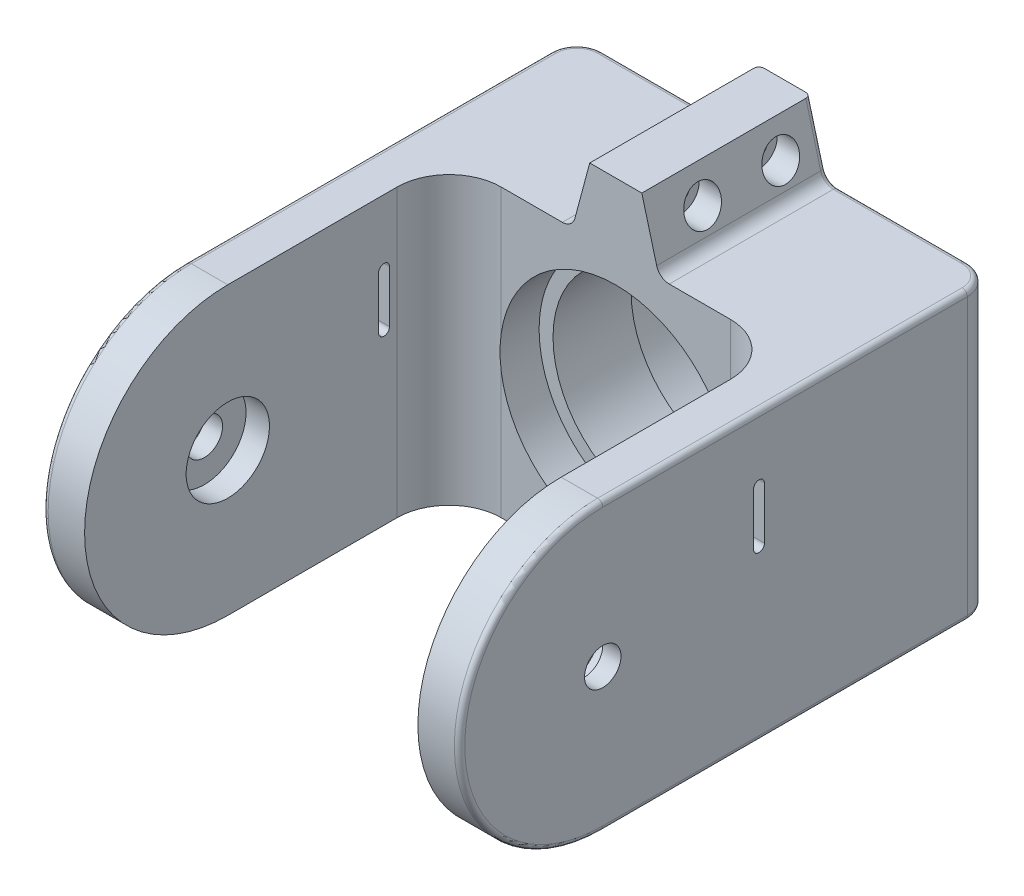
SolidWorks part; units mm, degrees
ref_plane "Front Plane" through (0, 0, 0) normal (0, 0, 1) x (1, 0, 0)
ref_plane "Top Plane" through (0, 0, 0) normal (0, 1, 0) x (1, 0, 0)
ref_plane "Right Plane" through (0, 0, 0) normal (1, 0, 0) x (0, 0, -1)
sketch "Sketch1" plane through (0, 0, 0) normal (0, 0, 1) x (1, 0, 0)
  circle A2 centre (0, 0) radius 44.45
  circle A3 centre (0, 0) radius 44.45 construction
  circle A4 centre (0, 0) radius 39.1
  circle A5 centre (0, 0) radius 38.1 construction
  dimension "D1" = 1
extrude "Centre Hole for L2" add sketch "Sketch1" along normal blind 30 contours A4 | A2
sketch "Sketch2" plane through (0, 0, 30) normal (0, 0, 1) x (1, 0, 0)
  line L0 (0, 48.4974) -> (0, 0) construction
  line L5 (-80, 55) -> (-80, -55)
  line L12 (0, 0) -> (72.986, 0) construction
  line L16 (-80, 55) -> (80, 55)
  line L17 (80, 55) -> (80, -55)
  line L18 (-80, -55) -> (80, -55)
  circle A0 centre (0, 0) radius 44.45
  circle A1 centre (0, 0) radius 44.45 construction
  circle A5 centre (0, 0) radius 44.45
  point P13 (0, 55)
  dimension "D1" = 80
  dimension "D2" = 110
extrude "Main Structure" add sketch "Sketch2" along normal blind 100 and the other way blind 50 separate body contours L5 L18 L17 L16 | A5
sketch "Sketch3" plane through (-80, 0, 0) normal (-1, 0, 0) x (0, 0, 1)
  line L0 (130, 55) -> (130, -55) construction
  line L1 (130, 55) -> (130, -55)
  line L2 (-20, 55) -> (130, 55) construction
  arc A0 (130, 55) -> (130, -55) centre (130, 0) cw
extrude "Bearing Curve" add sketch "Sketch3" against normal blind 16 contours A0 L1
mirror "Upright Mirror" about plane through (0, 0, 0) normal (1, 0, 0) of "Bearing Curve"
sketch "Sketch6" plane through (-80, 0, 0) normal (-1, 0, 0) x (0, 0, 1)
  circle A0 centre (130, 0) radius 7
  dimension "D1" = 14
extrude "Shaft Hole" cut sketch "Sketch6" against normal up to surface (16 mm away) up to face at (-64, 0, 157.5)
sketch "Sketch4" plane through (0, 55, 0) normal (0, 1, 0) x (1, 0, 0)
  line L0 (0, -110) -> (0, 20) construction
  line L1 (-64, -130) -> (64, -130) construction
  line L2 (-80, 20) -> (80, 20) construction
  line L3 (-64, -130) -> (-64, -65)
  line L4 (-44, -45) -> (44, -45)
  line L5 (-64, -130) -> (64, -130)
  line L6 (64, -130) -> (64, -65)
  arc A0 (-64, -65) -> (-44, -45) centre (-44, -65) cw
  arc A1 (64, -65) -> (44, -45) centre (44, -65) ccw
  point P17 (0, -130)
  point P20 (0, -45)
  dimension "D2" = 20
  dimension "D1" = 65
extrude "Wrist Cutout" cut sketch "Sketch4" against normal through all
sketch "Sketch9" plane through (-64, 0, 0) normal (1, 0, 0) x (0, 0, -1)
  circle A0 centre (-130, 0) radius 16
  dimension "D1" = 32
extrude "Bearing" cut sketch "Sketch9" against normal blind 9
mirror "Bearing Mirror" about plane through (0, 0, 0) normal (1, 0, 0) of "Shaft Hole", "Bearing"
fillet "Fillet2" radius 10 2 edges at (-80, 0, -20) (80, 0, -20)
sketch "Sketch10" plane through (0, 0, -20) normal (0, 0, -1) x (-1, 0, 0)
  line L0 (0, 55) -> (0, 80) construction
  line L1 (70, 55) -> (-70, 55) construction
  line L2 (10, 80) -> (-10, 80)
  line L3 (-10, 80) -> (-16.6987, 55)
  line L4 (-16.6987, 55) -> (16.6987, 55)
  line L5 (10, 80) -> (16.6987, 55)
  dimension "D1" = 25
  dimension "D2" = 10
  dimension "D3" = 75
extrude "Bolt Structure" add sketch "Sketch10" against normal up to surface (65 mm away) up to face at (0, -40.1897, 45)
sketch "Sketch11" plane through (0, 0, 0) normal (1, 0, 0) x (0, 0, -1)
  line L1 (-45, 67.5) -> (20, 67.5) construction
  line L2 (-45, 55) -> (-45, 80) construction
  line L3 (20, 80) -> (20, 55) construction
  circle A1 centre (5, 67.5) radius 3.1
  circle A2 centre (-25, 67.5) radius 3.1
  dimension "D1" = 6.2
  dimension "D2" = 15
  dimension "D3" = 30
extrude "Cut-Extrude6" cut sketch "Sketch11" against normal through all both and the other way through all
sketch "Sketch13" plane through (0, 0, 0) normal (1, 0, 0) x (0, 0, -1)
  circle A0 centre (5, 67.5) radius 7
  circle A1 centre (-25, 67.5) radius 7
  dimension "D1" = 14
extrude "Cut-Extrude8" cut sketch "Sketch13" along normal up to surface (8.3494 mm away) from offset 5 up to face at (14.18, 64.4, -5)
mirror "Mirror8" about plane through (0, 0, 0) normal (0, 1, 0) of "Cut-Extrude6", "Cut-Extrude8", "Bolt Structure"
fillet "Fillet3" radius 5 4 edges at (-16.6987, -55, 12.5) (16.6987, -55, 12.5) (-16.6987, 55, 12.5) (16.6987, 55, 12.5)
fillet "Fillet1" radius 2 22 edges at (-80, 55, 60) (-80, -55, 60) (80, -55, 60) (80, 55, 60) (-80, 0, 185) (-12.8529, -69.353, -20) (-17.4916, -56.0332, -20) (-45.2677, -55, -20) (-77.0711, -55, -17.0711) (-12.8529, 69.353, -20) (-17.4916, 56.0332, -20) (-45.2677, 55, -20) (-77.0711, 55, -17.0711) (12.8529, 69.353, -20) (17.4916, 56.0332, -20) (45.2677, 55, -20) (77.0711, 55, -17.0711) (12.8529, -69.353, -20) (17.4916, -56.0332, -20) (45.2677, -55, -20) (77.0711, -55, -17.0711) (80, 0, 185)
sketch "Sketch14" plane through (-80, 0, 0) normal (-1, 0, 0) x (0, 0, 1)
  line L0 (70, 30) -> (70, 10) construction
  line L1 (72.1, 30) -> (72.1, 10)
  line L2 (67.9, 30) -> (67.9, 10)
  arc A0 (72.1, 30) -> (67.9, 30) centre (70, 30) ccw
  arc A1 (67.9, 10) -> (72.1, 10) centre (70, 10) ccw
  point P2 (70, 20)
  dimension "D1" = 4.2
  dimension "D2" = 20
  dimension "D3" = 10
  dimension "D4" = 70
extrude "Tensioner Slot" cut sketch "Sketch14" against normal up to surface (16 mm away) up to face at (-64, 0, 114)
mirror "Mirror9" about plane through (0, 0, 0) normal (1, 0, 0) of "Tensioner Slot"
